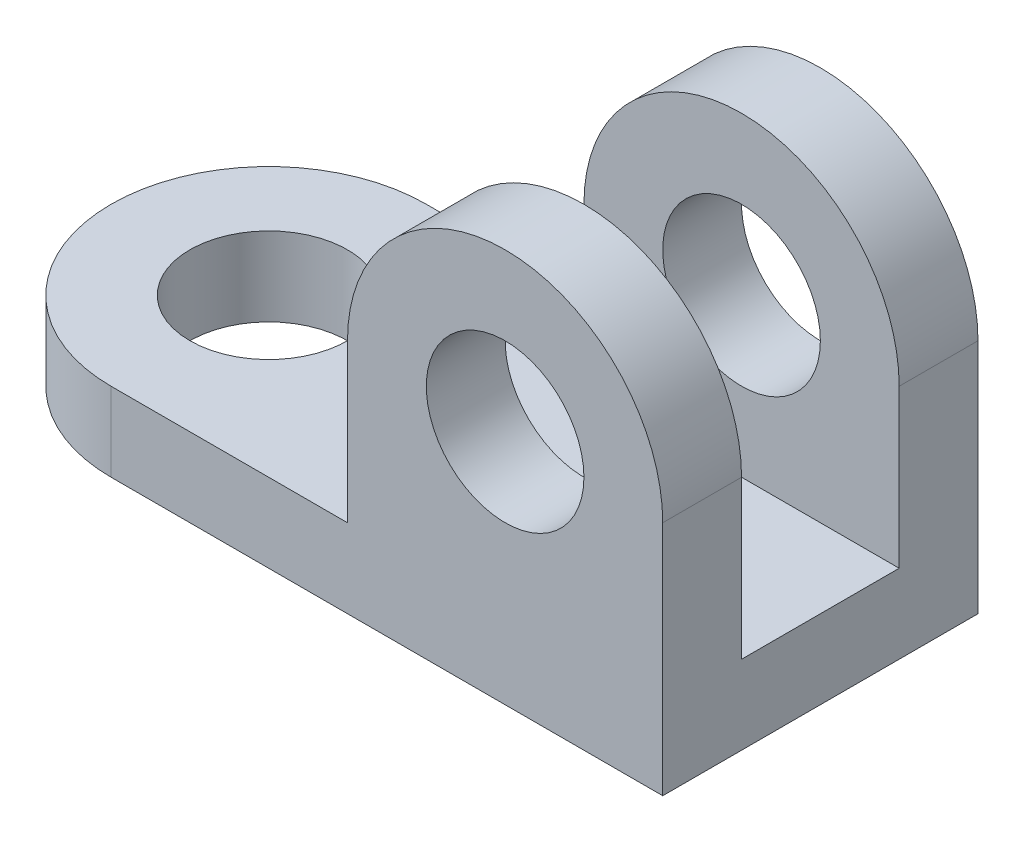
SolidWorks part; units mm, degrees
material "Brass"
ref_plane "Front Plane" through (0, 0, 0) normal (0, 0, 1) x (1, 0, 0)
ref_plane "Top Plane" through (0, 0, 0) normal (0, 1, 0) x (1, 0, 0)
ref_plane "Right Plane" through (0, 0, 0) normal (1, 0, 0) x (0, 0, -1)
sketch "Croquis2" plane through (0, 0, 0) normal (0, 1, 0) x (1, 0, 0)
  line L0 (0, 0) -> (0, 50.8)
  line L1 (0, 50.8) -> (-88.9, 50.8)
  line L3 (-88.9, 0) -> (0, 0)
  arc A0 (-88.9, 50.8) -> (-88.9, 0) centre (-88.9, 25.4) ccw
  circle A1 centre (-88.9, 25.4) radius 12.7
  dimension "D2" = 25.4
  dimension "D3" = 25.4
  dimension "D1" = 88.9
extrude "Saliente-Extruir1" add sketch "Croquis2" along normal blind 12.7
sketch "Croquis4" plane through (0, 0, 0) normal (0, 0, 1) x (1, 0, 0)
  line L0 (0, 12.7) -> (0, 38.1)
  line L2 (-50.8, 38.1) -> (-50.8, 12.7)
  line L3 (-88.9, 12.7) -> (0, 12.7) construction
  line L4 (-50.8, 12.7) -> (0, 12.7)
  arc A0 (0, 38.1) -> (-50.8, 38.1) centre (-25.4, 38.1) ccw
  circle A1 centre (-25.4, 38.1) radius 12.7
  dimension "D1" = 25.4
  dimension "D2" = 25.4
  dimension "D3" = 25.4
extrude "Saliente-Extruir4" add sketch "Croquis4" against normal through all
extrude "Cortar-Extruir1" cut sketch "Croquis4<5>" against normal blind 25.4 from offset 12.7 offset against normal yes
sketch "Croquis4<5>" plane through (0, 0, 0) normal (0, 0, 1) x (1, 0, 0) same geometry as "Croquis4"
